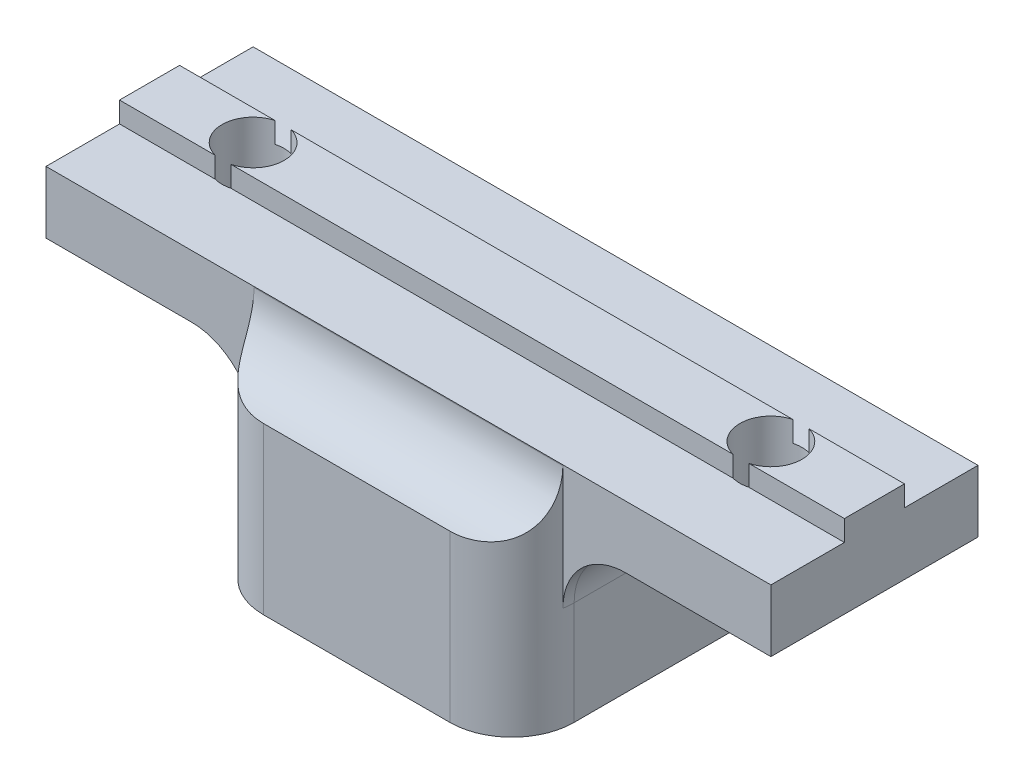
SolidWorks part; units mm, degrees
ref_plane "Front Plane" through (0, 0, 0) normal (0, 0, 1) x (1, 0, 0)
ref_plane "Top Plane" through (0, 0, 0) normal (0, 1, 0) x (1, 0, 0)
ref_plane "Right Plane" through (0, 0, 0) normal (1, 0, 0) x (0, 0, -1)
sketch "Sketch3" plane through (0, 0, 0) normal (0, 1, 0) x (1, 0, 0)
  line L1 (-7.5, -7.5) -> (7.5, -7.5)
  line L2 (-7.5, -7.5) -> (-7.5, 7.5)
  line L3 (-7.5, 7.5) -> (7.5, 7.5)
  line L4 (7.5, -7.5) -> (7.5, 7.5)
  point P4 (-7.5, 0)
  point P7 (0, 7.5)
  dimension "D1" = 15
  dimension "D2" = 15
extrude "MagnetSupport" add sketch "Sketch3" along normal blind 8
fillet "Fillet5" radius 3 4 edges at (-7.5, 4, -7.5) (7.5, 4, -7.5) (-7.5, 4, 7.5) (7.5, 4, 7.5)
sketch "Sketch5" plane through (0, 8, 0) normal (0, 1, 0) x (1, 0, 0)
  line L0 (-9.5741, 0) -> (9.5741, 0) construction
  line L1 (-17.5, 5) -> (17.5, 5)
  line L2 (-17.5, 5) -> (-17.5, -5)
  line L3 (-17.5, -5) -> (17.5, -5)
  line L4 (17.5, 5) -> (17.5, -5)
  line L5 (0, -6.6) -> (0, 6.6) construction
  point P6 (-17.5, 0)
  point P9 (0, 5)
  dimension "D1" = 10
  dimension "D2" = 35
extrude "Boss-Extrude1" add sketch "Sketch5" along normal blind 3
fillet "Fillet6" radius 3 6 edges at (7.4895, 8, 4.7509) (7.4895, 8, -4.7509) (-7.4895, 8, -4.7509) (-7.4895, 8, 4.7509) (7.5, 8, 0) (-7.5, 8, 0)
sketch "Sketch6" plane through (-17.5, 0, 0) normal (-1, 0, 0) x (0, 0, 1)
  line L0 (-5, 11) -> (5, 11) construction
  line L1 (-1.45, 11) -> (1.45, 11)
  line L2 (-1.45, 11) -> (-1.45, 12)
  line L3 (-1.45, 12) -> (1.45, 12)
  line L4 (1.45, 11) -> (1.45, 12)
  line L5 (0, -9.5741) -> (0, 9.5741) construction
  point P6 (0, 12)
  dimension "D1" = 2.9
  dimension "D2" = 1
extrude "Boss-Extrude2" add sketch "Sketch6" against normal up to surface (35 mm away) up to face at (17.5, 9.5, 0)
sketch "Sketch7" plane through (0, 8, 0) normal (0, -1, 0) x (-1, 0, 0)
  line L0 (-9.5741, 0) -> (9.5741, 0) construction
  line L2 (17.5, -1.45) -> (17.5, 1.45) construction
  line L3 (-17.5, 1.45) -> (-17.5, -1.45) construction
  circle A0 centre (12.5, 0) radius 1.5
  circle A1 centre (-12.5, 0) radius 1.5
  dimension "D1" = 5
  dimension "D2" = 3
  dimension "D3" = 5
extrude "Cut-Extrude1" cut sketch "Sketch7" against normal through all
fillet "Fillet7" radius 3 2 edges at (0, 8, -5) (0, 8, 5)
sketch "Sketch4" plane through (0, 0, 0) normal (0, -1, 0) x (1, 0, 0)
  circle A0 centre (0, 0) radius 6.25
  dimension "D1" = 12.5
extrude "MagnetBigHole" cut sketch "Sketch4" against normal blind 8
